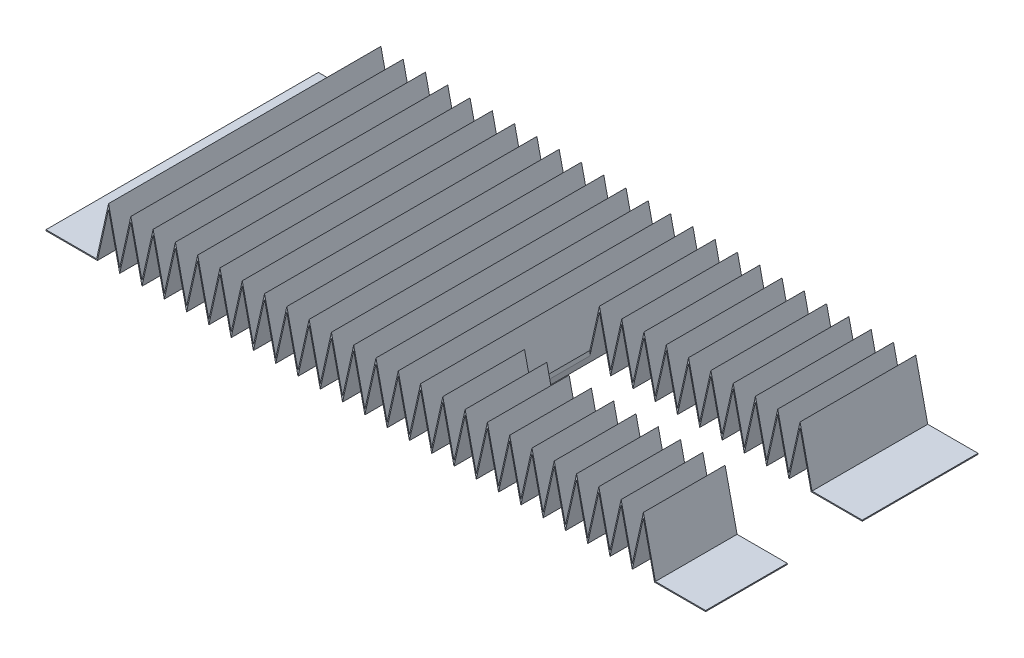
SolidWorks part; units mm, degrees
ref_plane "Front Plane" through (0, 0, 0) normal (0, 0, 1) x (1, 0, 0)
ref_plane "Top Plane" through (0, 0, 0) normal (0, 1, 0) x (1, 0, 0)
ref_plane "Right Plane" through (0, 0, 0) normal (1, 0, 0) x (0, 0, -1)
sketch "Sketch1" plane through (0, 0, 0) normal (0, 0, 1) x (1, 0, 0)
  line L0 (0, 0) -> (3.273, 14.741)
  line L1 (3.273, 14.741) -> (6.546, 0)
  line L2 (0, 0) -> (511, 0) construction
  line L3 (6.546, 0) -> (9.819, 14.741)
  line L4 (9.819, 14.741) -> (13.092, 0)
  line L5 (13.092, 0) -> (16.365, 14.741)
  line L6 (16.365, 14.741) -> (19.638, 0)
  line L7 (19.638, 0) -> (22.911, 14.741)
  line L8 (22.911, 14.741) -> (26.184, 0)
  line L9 (26.184, 0) -> (29.457, 14.741)
  line L10 (29.457, 14.741) -> (32.73, 0)
  line L11 (32.73, 0) -> (36.003, 14.741)
  line L12 (36.003, 14.741) -> (39.276, 0)
  line L13 (39.276, 0) -> (42.549, 14.741)
  line L14 (42.549, 14.741) -> (45.822, 0)
  line L15 (45.822, 0) -> (49.095, 14.741)
  line L16 (49.095, 14.741) -> (52.368, 0)
  line L17 (52.368, 0) -> (55.641, 14.741)
  line L18 (55.641, 14.741) -> (58.914, 0)
  line L19 (0, 0) -> (-15.1, 0)
  line L20 (58.914, 0) -> (62.187, 14.741)
  line L21 (62.187, 14.741) -> (65.46, 0)
  line L22 (65.46, 0) -> (68.733, 14.741)
  line L23 (68.733, 14.741) -> (72.006, 0)
  line L24 (72.006, 0) -> (75.279, 14.741)
  line L25 (75.279, 14.741) -> (78.552, 0)
  line L26 (78.552, 0) -> (81.825, 14.741)
  line L27 (81.825, 14.741) -> (85.098, 0)
  line L28 (85.098, 0) -> (88.371, 14.741)
  line L29 (88.371, 14.741) -> (91.644, 0)
  line L30 (91.644, 0) -> (94.917, 14.741)
  line L31 (94.917, 14.741) -> (98.19, 0)
  line L32 (98.19, 0) -> (101.463, 14.741)
  line L33 (101.463, 14.741) -> (104.736, 0)
  line L34 (104.736, 0) -> (108.009, 14.741)
  line L35 (108.009, 14.741) -> (111.282, 0)
  line L36 (111.282, 0) -> (114.555, 14.741)
  line L37 (114.555, 14.741) -> (117.828, 0)
  line L38 (80.65, -119) -> (80.65, 132.963) construction
  line L39 (117.828, 0) -> (121.101, 14.741)
  line L40 (121.101, 14.741) -> (124.374, 0)
  line L41 (124.374, 0) -> (127.647, 14.741)
  line L42 (127.647, 14.741) -> (130.92, 0)
  line L43 (130.92, 0) -> (134.193, 14.741)
  line L44 (134.193, 14.741) -> (137.466, 0)
  line L45 (137.466, 0) -> (140.739, 14.741)
  line L46 (140.739, 14.741) -> (144.012, 0)
  line L47 (144.012, 0) -> (147.285, 14.741)
  line L48 (147.285, 14.741) -> (150.558, 0)
  line L49 (150.558, 0) -> (153.831, 14.741)
  line L51 (153.831, 14.741) -> (157.104, 0)
  line L52 (157.104, 0) -> (160.377, 14.741)
  line L53 (160.377, 14.741) -> (163.65, 0)
  line L54 (163.65, 0) -> (178.65, 0)
  dimension "D1" = 511
  dimension "D2" = 15.1
  dimension "D3" = 15
  dimension "D4" = 6.546
  dimension "D6" = 98
  dimension "D5" = 25
extrude "Extrude-Thin1" add sketch "Sketch1" along normal mid plane 80 thin thin type one direction reverse wall 0.3
sketch "Sketch2" plane through (0, 0, 0) normal (0, 1, 0) x (1, 0, 0)
  line L1 (98.65, -16) -> (178.65, -16)
  line L2 (98.65, -16) -> (98.65, 6)
  line L3 (98.65, 6) -> (178.65, 6)
  line L4 (178.65, -16) -> (178.65, 6)
  line L5 (98.65, -16) -> (178.65, 6) construction
  line L6 (98.65, 6) -> (178.65, -16) construction
  line L8 (178.65, -40) -> (178.65, 40) construction
  point P0 (138.65, -5)
  dimension "D1" = 80
  dimension "D2" = 22
  dimension "D3" = 5
extrude "Cut-Extrude4" cut sketch "Sketch2" against normal through all and the other way through all contours L1 L4 L3 L2 region at (138.65, 0, 5)
